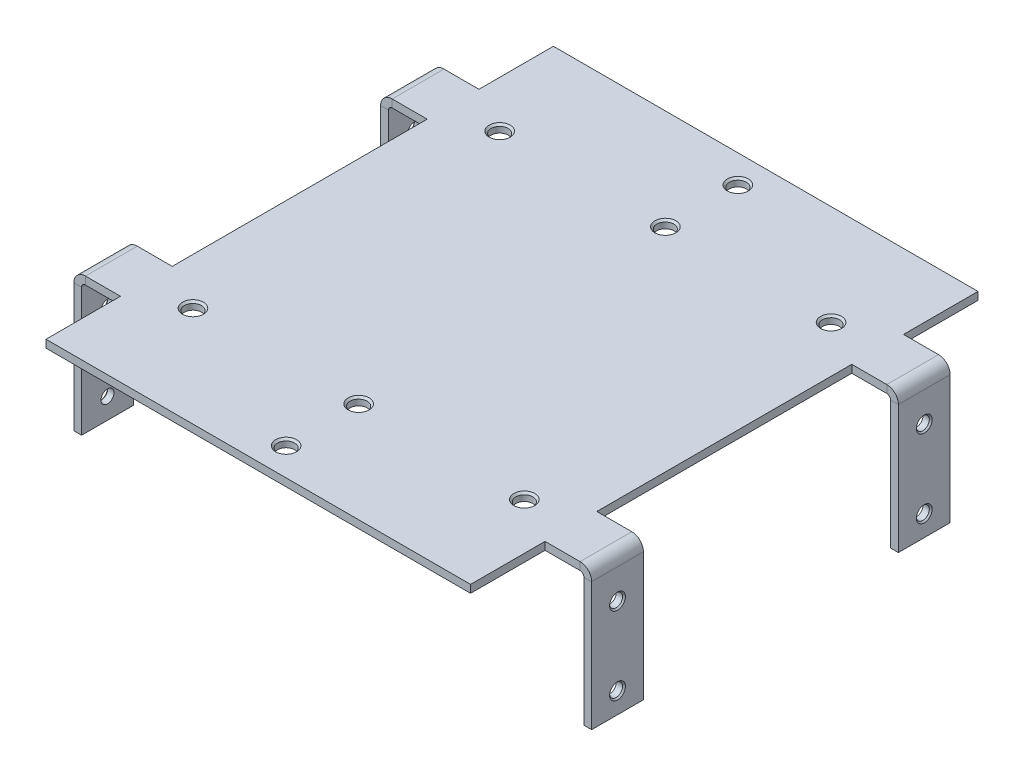
SolidWorks part; units mm, degrees
note: The reader was unsure of these and kept them because the rebuilt part matched: flange length of "Edge-Flange1".
ref_plane "Front" through (0, 0, 0) normal (0, 0, 1) x (1, 0, 0)
ref_plane "Top" through (0, 0, 0) normal (0, 1, 0) x (1, 0, 0)
ref_plane "Right" through (0, 0, 0) normal (1, 0, 0) x (0, 0, -1)
other "Configuration Table"
sketch "Sketch1" plane through (0, 0, 0) normal (0, 1, 0) x (1, 0, 0)
  line L0 (-41, -34.62) -> (-41, -49)
  line L1 (-41, 49) -> (41, 49)
  line L2 (-41, 49) -> (-41, 34.62)
  line L3 (-41, -49) -> (41, -49)
  line L4 (41, 49) -> (41, 34.62)
  line L5 (-41, 49) -> (41, -49) construction
  line L6 (-41, -49) -> (41, 49) construction
  line L7 (-41, -24.62) -> (-50, -24.62)
  line L9 (-41, -34.62) -> (-50, -34.62)
  line L10 (-50, -24.62) -> (-50, -34.62)
  line L11 (0, 77.147) -> (0, -89.1605) construction
  line L12 (-98.1301, 0) -> (83.8065, 0) construction
  line L13 (41, -34.62) -> (50, -34.62)
  line L14 (50, -24.62) -> (50, -34.62)
  line L15 (41, -24.62) -> (50, -24.62)
  line L16 (41, -34.62) -> (41, -49)
  line L17 (-41, 34.62) -> (-50, 34.62)
  line L18 (-50, 24.62) -> (-50, 34.62)
  line L19 (-41, 24.62) -> (-50, 24.62)
  line L20 (41, 34.62) -> (50, 34.62)
  line L21 (50, 24.62) -> (50, 34.62)
  line L22 (41, 24.62) -> (50, 24.62)
  line L23 (-41, 24.62) -> (-41, -24.62)
  line L24 (41, 24.62) -> (41, -24.62)
  point P0 (0, 0)
  dimension "D1" = 82
  dimension "D2" = 98
  dimension "D3" = 10
  dimension "D4" = 49.24
  dimension "D5" = 100
base flange "Base-Flange1" sketch "Sketch1" thickness 1.5 reverse thickness direction no parameters "D1"=0.7366
edge flange "Edge-Flange1" sketch "Sketch11" flange angle 90 flange length 27 flange position material inside bend radius 0.7366 thickness 1.5 relief rectangular parameters "D6"=10
sketch "Sketch11" plane through (-50, -1.5, 0) normal (1, 0, 0) x (0, 0, 1)
  line L2 (24.62, 0) -> (24.62, 25.5)
  line L3 (24.62, 25.5) -> (34.62, 25.5)
  line L4 (34.62, 25.5) -> (34.62, 0)
  line L5 (34.62, 0) -> (24.62, 0) construction
  line L6 (34.62, 0) -> (24.62, 0)
bend "EdgeBend1" bend radius 0.7366 bend angle 90 parameters "D5"=1
hole_wizard "M3 Tapped Hole1" positions "Sketch17" profile "Sketch14" tap size "M3" standard "ISO" end condition through all
sketch "Sketch17" plane through (-50, 0, 0) normal (-1, 0, 0) x (0, 0, 1)
  line L0 (29.62, 7.9076) -> (29.62, -38.1257) construction
  line L2 (34.62, -2.2366) -> (34.62, -27) construction
  line L3 (24.62, -27) -> (24.62, -2.2366) construction
  line L4 (34.62, -27) -> (24.62, -27) construction
  point P0 (29.62, -8)
  point P2 (29.62, -23)
  dimension "D1" = 15
  dimension "D2" = 4
sketch "Sketch14" plane through (-50, -8, 29.62) normal (0, 1, 0) x (0, 0, 1)
  line L0 (0, 0) -> (0, 100)
  line L1 (0, 100) -> (1.25, 100)
  line L2 (1.25, 100) -> (1.25, 0.275)
  line L3 (1.25, 0.275) -> (1.525, 0)
  line L5 (1.525, 0) -> (0, 0)
  line L6 (-1.25, 0.275) -> (-1.525, 0) construction
  line L11 (0, -6.35) -> (0, 107.95) construction
  dimension "Thru Tap Drill Dia." = 2.5
  dimension "Thru Tap Drill Depth" = 100
  dimension "Near C'Sink Dia." = 3.05
  dimension "Near C'Sink Angle" = 90
mirror "Mirror1" about plane through (0, 0, 0) normal (1, 0, 0) of "M3 Tapped Hole1", "Edge-Flange1"
bend "MirrorBend1" bend radius 0.7366 bend angle 90 parameters "D5"=2
mirror "Mirror2" about plane through (0, 0, 0) normal (0, 0, 1) of "Mirror1", "Edge-Flange1", "M3 Tapped Hole1"
bend "MirrorBend2" bend radius 0.7366 bend angle 90 parameters "D5"=3
bend "MirrorBend3" bend radius 0.7366 bend angle 90 parameters "D5"=4
hole_wizard "M4 Tapped Hole1" positions "Sketch21" profile "Sketch19" tap size "M4" standard "ISO" end condition through all
sketch "Sketch21" plane through (0, 0, 0) normal (0, 1, 0) x (1, 0, 0)
  line L0 (-58.3641, 29.62) -> (67.4311, 29.62) construction
  line L2 (-55.0878, -29.62) -> (59.2784, -29.62) construction
  line L4 (-41, 34.62) -> (-47.7634, 34.62) construction
  line L5 (-47.7634, 24.62) -> (-41, 24.62) construction
  line L6 (-41, -24.62) -> (-47.7634, -24.62) construction
  line L7 (-47.7634, -34.62) -> (-41, -34.62) construction
  line L8 (0, 64.6245) -> (0, -65.3034) construction
  point P0 (-32, 29.62)
  point P2 (0, 29.62)
  point P4 (32, 29.62)
  point P6 (-32, -29.62)
  point P8 (0, -29.62)
  point P10 (32, -29.62)
  point P42 (0, 43.62)
  point P44 (0, -43.62)
  dimension "D1" = 32
  dimension "D2" = 14
  dimension "D3" = 14
sketch "Sketch19" plane through (-32, 0, -29.62) normal (1, 0, 0) x (0, 0, 1)
  line L0 (0, 0) -> (0, 27)
  line L1 (0, 27) -> (1.65, 27)
  line L2 (1.65, 27) -> (1.65, 0.375)
  line L3 (1.65, 0.375) -> (2.025, 0)
  line L5 (2.025, 0) -> (0, 0)
  line L6 (-1.65, 0.375) -> (-2.025, 0) construction
  line L11 (0, -6.35) -> (0, 107.95) construction
  dimension "Thru Tap Drill Dia." = 3.3
  dimension "Thru Tap Drill Depth" = 27
  dimension "Near C'Sink Dia." = 4.05
  dimension "Near C'Sink Angle" = 90
sketch "Bend-Lines1" plane through (0, 0, 0) normal (0, 1, 0) x (1, 0, 0)
sketch "Bounding-Box1" plane through (0, 0, 0) normal (0, 1, 0) x (1, 0, 0)
sheet metal parameters "Sheet-Metal3" thickness 1.5 parameters "D1"=0.7366
flat pattern "Flat-Pattern3" [suppressed]
sketch "Bend-Lines2" plane through (0, 0, 0) normal (0, 1, 0) x (1, 0, 0)
sketch "Bounding-Box2" [suppressed] plane through (0, 0, 0) normal (0, 1, 0) x (1, 0, 0)
sheet metal parameters "Sheet-Metal4" thickness 1.5 parameters "D1"=0.7366
flat pattern "Flat-Pattern3" [suppressed]
sketch "Bend-Lines2" plane through (0, 0, 0) normal (0, 1, 0) x (1, 0, 0)
sketch "Bounding-Box2" [suppressed] plane through (0, 0, 0) normal (0, 1, 0) x (1, 0, 0)
bend of the flat pattern "Flatten-<EdgeBend1>1"
sheet metal parameters "Sheet-Metal5" thickness 1.5 parameters "D1"=0.7366
flat pattern "Flat-Pattern3" [suppressed]
sketch "Bend-Lines2" plane through (0, 0, 0) normal (0, 1, 0) x (1, 0, 0)
sketch "Bounding-Box2" [suppressed] plane through (0, 0, 0) normal (0, 1, 0) x (1, 0, 0)
bend of the flat pattern "Flatten-<EdgeBend1>1"
bend of the flat pattern "Flatten-<MirrorBend1>1"
sheet metal parameters "Sheet-Metal6" thickness 1.5 parameters "D1"=0.7366
flat pattern "Flat-Pattern3" [suppressed]
sketch "Bend-Lines2" plane through (0, 0, 0) normal (0, 1, 0) x (1, 0, 0)
sketch "Bounding-Box2" [suppressed] plane through (0, 0, 0) normal (0, 1, 0) x (1, 0, 0)
bend of the flat pattern "Flatten-<EdgeBend1>1"
bend of the flat pattern "Flatten-<MirrorBend1>1"
bend of the flat pattern "Flatten-<MirrorBend2>1"
bend of the flat pattern "Flatten-<MirrorBend3>1"
sheet metal parameters "Sheet-Metal7" thickness 1.5 parameters "D1"=0.7366
flat pattern "Flat-Pattern3" [suppressed]
sketch "Bend-Lines2" plane through (0, 0, 0) normal (0, 1, 0) x (1, 0, 0)
sketch "Bounding-Box2" [suppressed] plane through (0, 0, 0) normal (0, 1, 0) x (1, 0, 0)
bend of the flat pattern "Flatten-<EdgeBend1>1"
sheet metal parameters "Sheet-Metal8" thickness 1.5 parameters "D1"=0.7366
flat pattern "Flat-Pattern3" [suppressed]
sketch "Bend-Lines2" plane through (0, 0, 0) normal (0, 1, 0) x (1, 0, 0)
sketch "Bounding-Box2" [suppressed] plane through (0, 0, 0) normal (0, 1, 0) x (1, 0, 0)
bend of the flat pattern "Flatten-<EdgeBend1>1"
bend of the flat pattern "Flatten-<MirrorBend1>1"
bend of the flat pattern "Flatten-<MirrorBend2>1"
bend of the flat pattern "Flatten-<MirrorBend3>1"
equation "\"D3@Sketch21\" = \"D2@Sketch21\""
